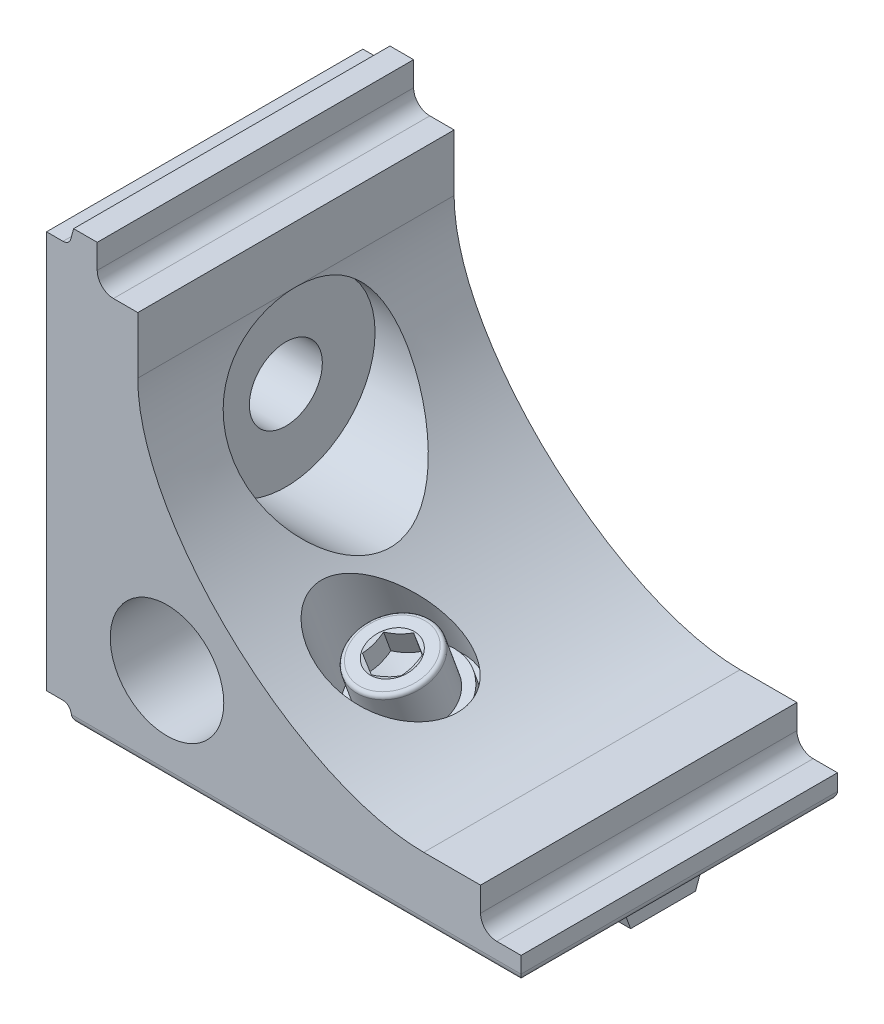
SolidWorks part; units mm, degrees
ref_plane "Front Plane" through (0, 0, 0) normal (0, 0, 1) x (1, 0, 0)
ref_plane "Top Plane" through (0, 0, 0) normal (0, 1, 0) x (1, 0, 0)
ref_plane "Right Plane" through (0, 0, 0) normal (1, 0, 0) x (0, 0, -1)
sketch "Sketch1" plane through (0, 0, 0) normal (0, 0, 1) x (1, 0, 0)
  line L0 (29.25, 0) -> (-29.25, 0) construction
  line L1 (-29.25, 0) -> (-29.25, 53) construction
  line L2 (-12.5, -2.9) -> (12.5, -2.9) construction
  point P3 (0, 0)
  point P8 (0, -2.9)
  dimension "Height" = 53
  dimension "Offset" = 29.25
  dimension "D1" = 2.9
  dimension "Length" = 25
sketch "Sketch2" plane through (0, 0, 0) normal (1, 0, 0) x (0, 0, -1)
  line L0 (-19.5, 0) -> (19.5, 0) construction
  line L1 (-3, -2.9) -> (3, -2.9) construction
  line L3 (0, 0) -> (0, 53) construction
  line L4 (3, -2.9) -> (3, -3.9) construction
  circle A0 centre (0, 30) radius 11 construction
  circle A1 centre (0, 30) radius 4.5 construction
  point P4 (0, 0)
  point P8 (0, -2.9)
  dimension "D3" = 9
  dimension "Mounting Hole Diameter" = 22
  dimension "Width" = 39
  dimension "Thread Size" = 6
  dimension "Thread Pitch" = 1
  dimension "D2" = 30
sketch "Sketch3" plane through (0, 0, 0) normal (0, 0, 1) x (1, 0, 0)
  line L0 (-29.25, 2) -> (-29.25, 51)
  line L1 (-29.25, 0) -> (-29.25, 53) construction
  line L2 (-29.25, 51) -> (-26.45, 51)
  line L3 (-26.45, 51) -> (-25.9141, 53)
  line L4 (-25.9141, 53) -> (-23, 53)
  line L5 (-23, 53) -> (-23, 48)
  line L6 (-23, 48) -> (-18, 48)
  line L7 (-18, 48) -> (-18, 41)
  line L8 (-29.25, 2) -> (-26.45, 2)
  line L9 (-26.45, 2) -> (-25.9141, 0)
  line L10 (29.25, 0) -> (-29.25, 0) construction
  line L11 (-25.9141, 0) -> (29.25, 0)
  line L12 (29.25, 0) -> (29.25, 3)
  line L13 (29.25, 3) -> (24.25, 3)
  line L14 (24.25, 3) -> (24.25, 8)
  line L15 (24.25, 8) -> (17.25, 8)
  line L16 (-18, 41) -> (-18, 25.7234) construction
  line L17 (-18, 25.7234) -> (1.9734, 8) construction
  line L18 (1.9734, 8) -> (17.25, 8) construction
  line L19 (-14.4, 4.6) -> (-14.4, 0) construction
  line L20 (-14.4, 11.6) -> (-8.0133, 16.8617) construction
  line L21 (-8.9973, 16.051) -> (-5.9101, 18.5944) construction
  line L22 (-21.4, 11.6) -> (-29.25, 11.6) construction
  circle A0 centre (-14.4, 11.6) radius 7
  spline S0 degree 3 poles (-18, 41) (-18, 25.7234) (1.9734, 8) (17.25, 8) knots 0 0 0 0 1 1 1 1
  dimension "D10" = 4.6
  dimension "D11" = 14
  dimension "D1" = 12
  dimension "D2" = 5
  dimension "D3" = 8
  dimension "D4" = 49
  dimension "D5" = 105
  dimension "D6" = 12
  dimension "D7" = 5
  dimension "D8" = 11.25
  dimension "D9" = 2.8
  dimension "D12" = 4
  dimension "D13" = 7.85
extrude "Boss-Extrude1" add sketch "Sketch3" along normal mid plane 39
sketch "Sketch4" plane through (0, 0, 0) normal (1, 0, 0) x (0, 0, -1)
  circle A0 centre (0, 30) radius 4.5 construction
  circle A1 centre (0, 30) radius 4.5
extrude "Cut-Extrude1" cut sketch "Sketch4" against normal through all
sketch "Sketch5" plane through (0, 0, 0) normal (1, 0, 0) x (0, 0, -1)
  circle A0 centre (0, 30) radius 11 construction
  circle A1 centre (0, 30) radius 11
extrude "Cut-Extrude2" cut sketch "Sketch5" against normal offset from surface (19.25 mm away) 10 up to face at (-29.25, 30, -4.5)
sketch "Sketch6" plane through (0, 0, 0) normal (1, 0, 0) x (0, 0, -1)
  line L0 (-4, -2.9) -> (4, -2.9)
  line L2 (4, -2.9) -> (5.0555, 0)
  line L3 (-19.5, 0) -> (19.5, 0) construction
  line L4 (5.0555, 0) -> (-5.0555, 0)
  line L5 (-5.0555, 0) -> (-4, -2.9)
  line L6 (0, 0) -> (0, 53) construction
  point P3 (0, -2.9)
  dimension "D1" = 8
  dimension "D2" = 20
extrude "Boss-Extrude2" add sketch "Sketch6" along normal offset from surface 2 and the other way offset from surface 5 up to face at (29.25, 1.5, 0) other way up to face at (-29.25, 30, -4.5)
fillet "Fillet1" radius 2 2 edges at (-23, 48, 0) (24.25, 3, 0)
fillet "Fillet2" radius 1 6 edges at (1.6679, 0, -19.5) (29.25, 0, 0) (1.6679, 0, 19.5) (-25.9141, 0, 0) (-26.45, 2, 0) (-26.45, 51, 0)
sketch "Sketch7" plane through (0, 0, 0) normal (1, 0, 0) x (0, 0, -1)
  line B0 (5.9518, -10.4811) -> (7.2578, -9.1838)
  line B1 (7.8162, -4.7642) -> (5.5241, -5.5446)
  line B2 (5.5241, -5.5446) -> (4, -2.9)
  line B3 (4, -2.9) -> (-4, -2.9)
  line B4 (-4, -2.9) -> (-5.5262, -5.5434)
  line B5 (-5.5262, -5.5434) -> (-7.8014, -4.7153)
  line B6 (-7.2827, -9.135) -> (-5.9855, -10.4409)
  line B7 (0.3137, -12.5332) -> (5.9518, -10.4811)
  line B8 (0, -2.9) -> (0, -5.4471) construction
  arc B9 (7.2578, -9.1838) -> (8.808, -5.4767) centre (3.558, -5.4591) ccw
  arc B10 (8.808, -5.4767) -> (7.8162, -4.7642) centre (8.058, -5.4742) ccw
  arc B11 (-7.8014, -4.7153) -> (-8.808, -5.4175) centre (-8.058, -5.42) ccw
  arc B12 (-8.808, -5.4175) -> (-7.2827, -9.135) centre (-3.558, -5.4351) ccw
  arc B13 (-5.9855, -10.4409) -> (0.3137, -12.5332) centre (-0.7667, -5.2571) ccw
sketch_block_instance "Block-Sketch6-1"
sketch_block "Block-Sketch6" parameters "D1"=0.75, "D10"=5.25, "D2"=70, "D3"=0.193, "D4"=30, "D5"=20, "D6"=6, "D7"=8, "D8"=17.6159, "D9"=9.1595, "D11"=45, "D12"=45
extrude "Boss-Extrude3" add sketch "Sketch7" along normal mid plane 25 separate body
sketch "Sketch8" plane through (0, 0, 0) normal (1, 0, 0) x (0, 0, -1)
  line L0 (3.1327, -11.5071) -> (-8.2601, 19.7945)
  line L1 (0.3137, -12.5332) -> (5.9518, -10.4811) construction
  line L2 (-8.2601, 19.7945) -> (-14.603, 17.4859)
  line L3 (-14.603, 17.4859) -> (-9.9858, 4.8)
  line L4 (-9.9858, 4.8) -> (-6.4619, 6.0826)
  line L5 (-6.4619, 6.0826) -> (0.3137, -12.5332)
  line L6 (0.3137, -12.5332) -> (3.1327, -11.5071)
  line L7 (-6.9703, 16.2507) -> (3.1327, -11.5071) construction
  line L8 (-19.5, 0) -> (19.5, 0) construction
  dimension "D1" = 6
  dimension "D2" = 4.8
  dimension "D3" = 13.5
  dimension "D4" = 13.5
revolve "Cut-Revolve1" cut sketch "Sketch8" angle 360 about L7
sketch "Sketch9" plane through (0, 0, 0) normal (1, 0, 0) x (0, 0, -1)
  line L0 (3.1327, -11.5071) -> (-4.667, 9.9224)
  line L1 (3.1327, -11.5071) -> (-8.2601, 19.7945) construction
  line L2 (-4.667, 9.9224) -> (-7.3962, 10.4036)
  line L3 (-7.3962, 10.4036) -> (-8.3812, 13.11)
  line L4 (-8.3812, 13.11) -> (-10.6364, 12.2891)
  line L5 (-10.6364, 12.2891) -> (-8.6664, 6.8765)
  line L6 (-8.6664, 6.8765) -> (-6.975, 7.4921)
  line L7 (-6.975, 7.4921) -> (0.04, -11.7814)
  line L8 (0.04, -11.7814) -> (1.0654, -12.2596)
  line L9 (0.3137, -12.5332) -> (3.1327, -11.5071) construction
  line L10 (1.0654, -12.2596) -> (3.1327, -11.5071)
  line L11 (-4.667, 9.9224) -> (-8.2601, 19.7945) construction
  line L12 (-6.4619, 6.0826) -> (-9.3515, 5.0309)
  line L13 (-9.9858, 4.8) -> (-6.4619, 6.0826) construction
  line L14 (-9.3515, 5.0309) -> (-9.8645, 6.4404)
  line L15 (-9.8645, 6.4404) -> (-8.6664, 6.8765)
  line L16 (-68410.9989, 187954.7748) -> (68407.1614, -187950.0313) construction
  dimension "D1" = 6
  dimension "D2" = 4.8
  dimension "D3" = 12.15
  dimension "D4" = 1.5
  dimension "D5" = 9.6
  dimension "D6" = 5.76
  dimension "D7" = 60
  dimension "D8" = 2.88
  dimension "D9" = 45
  dimension "D10" = 0.8
revolve "Revolve1" add sketch "Sketch9" angle 360 about L11 region at (0, 0.7451, 3.2798)
revolve "Revolve2" add sketch "Sketch9<3>" angle 360 about L11 region at (0, 6.2615, 8.1632)
sketch "Sketch9<3>" plane through (0, 0, 0) normal (1, 0, 0) x (0, 0, -1) same geometry as "Sketch9"
sketch "Sketch10" plane through (0, 14.27, 5.1939) normal (0, 0.9397, 0.342) x (1, 0, 0)
  line L1 (0, 1.7794) -> (-2.4, 0.3938)
  line L2 (-2.4, 0.3938) -> (-2.4, -2.3775)
  line L3 (-2.4, -2.3775) -> (0, -3.7631)
  line L4 (0, -3.7631) -> (2.4, -2.3775)
  line L5 (2.4, -2.3775) -> (2.4, 0.3938)
  line L6 (2.4, 0.3938) -> (0, 1.7794)
  circle A0 centre (0, -0.9919) radius 2.4 construction
  circle A1 centre (0, -0.9919) radius 2.4 construction
extrude "Cut-Extrude3" cut sketch "Sketch10" against normal up to surface (2.6656 mm away) up to face at (0, 12.0453, 2.8856)
sketch "Sketch11" plane through (0, 14.27, 5.1939) normal (0, 0.9397, 0.342) x (1, 0, 0)
  circle A0 centre (0, -0.9919) radius 2.88
  dimension "D1" = 5.76
extrude "Cut-Extrude4" cut sketch "Sketch11" against normal through all draft 60
fillet "Fillet3" radius 0.5 1 edges at (0, 15.5725, 1.6154)
equation "\"D1@Boss-Extrude1\"=\"Width@Sketch2\""
equation "\"D1@Boss-Extrude3\"=\"Length@Sketch1\""
equation "\"D1@Sketch8\"=\"Thread Size@Sketch2\""
equation "\"D2@Sketch8\"=\"D1@Sketch8\"*.8"
equation "\"D3@Sketch8\"=\"D1@Sketch8\"*2.25"
equation "\"D4@Sketch8\"=\"D3@Sketch8\""
equation "\"D1@Sketch9\"=\"Thread Size@Sketch2\""
equation "\"D2@Sketch9\"=\"D1@Sketch9\"*.8"
equation "\"D3@Sketch9\"=\"D3@Sketch8\"*.9"
equation "\"D4@Sketch9\"=\"D1@Sketch9\"*.25"
equation "\"D5@Sketch9\"=\"D2@Sketch9\"*2"
equation "\"D6@Sketch9\"=\"D5@Sketch9\"*.6"
equation "\"D8@Sketch9\"=\"D6@Sketch9\"*.5"
equation "\"D10@Sketch9\"=\"Thread Pitch@Sketch2\"*.8"
equation "\"D1@Sketch11\"=\"D2@Sketch9\"*1.2"
